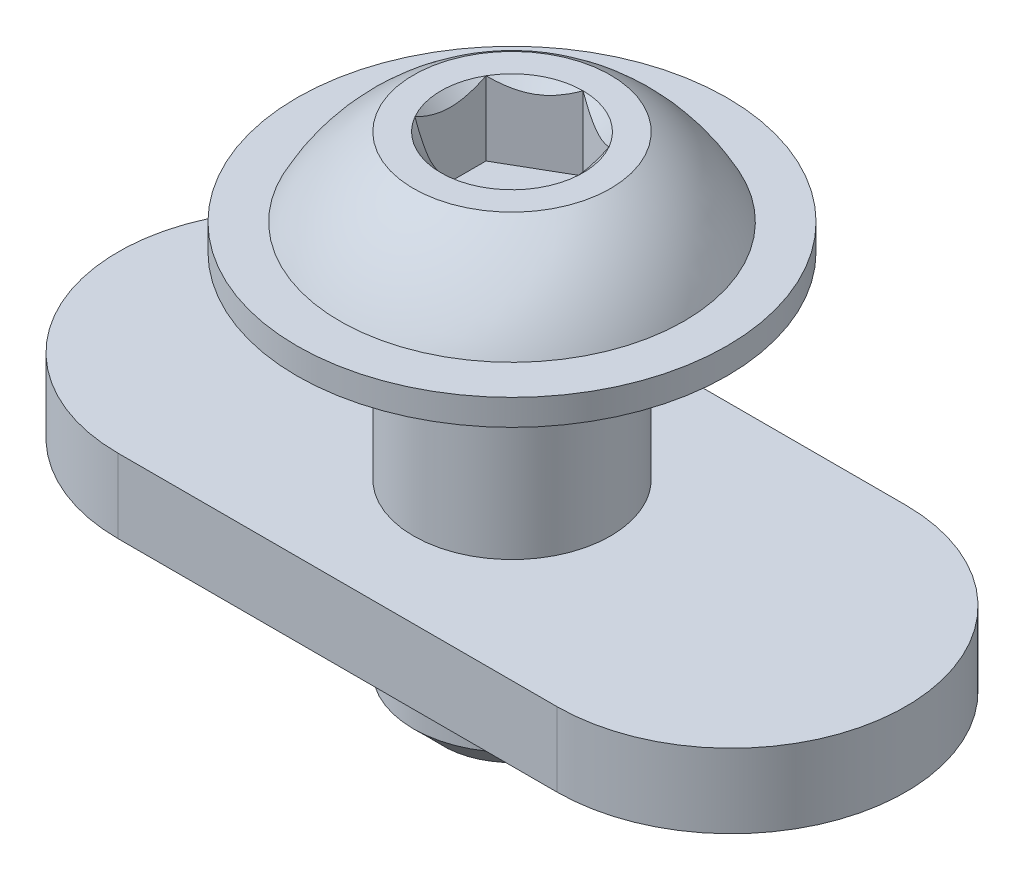
SolidWorks part; units mm, degrees
ref_plane "Front Plane" through (0, 0, 0) normal (0, 0, 1) x (1, 0, 0)
ref_plane "Top Plane" through (0, 0, 0) normal (0, 1, 0) x (1, 0, 0)
ref_plane "Right Plane" through (0, 0, 0) normal (1, 0, 0) x (0, 0, -1)
sketch "Sketch1" plane through (0, 0, 0) normal (0, 1, 0) x (1, 0, 0)
  circle A0 centre (0, 0) radius 3.175
  point P3 (-3.175, 0)
  point P4 (3.175, 0)
  dimension "D1" = 6.35
extrude "Boss-Extrude1" add sketch "Sketch1" against normal blind 12.7
sketch "Sketch2" plane through (0, -12.7, 0) normal (0, -1, 0) x (1, 0, 0)
  circle A1 centre (0, 0) radius 3.175
  circle A2 centre (0, 0) radius 3.175
  point P0 (0, -3.175)
  dimension "D1" = 0
curve "Helix/Spiral1" [suppressed] pitch 1.27 height 13.97 turns 11
sketch "Sketch3" plane through (0, 0, 0) normal (1, 0, 0) x (0, 0, -1)
  line L0 (3.3125, -12.6206) -> (2.2126, -13.2556) construction
  line L1 (2.2126, -13.2556) -> (3.3125, -13.8906) construction
  line L2 (3.3125, -13.8906) -> (3.3125, -12.6206) construction
  line L3 (2.3501, -13.1762) -> (2.3501, -13.335) construction
  line L4 (3.175, -12.7) -> (3.175, -13.8112) construction
  line L5 (2.2126, -13.2556) -> (2.3501, -13.2556) construction
  line L6 (3.175, -13.2556) -> (3.3125, -13.2556) construction
  line L8 (2.2126, -13.2556) -> (-3.175, -13.2556) construction
  line L9 (2.3501, -13.1762) -> (3.2437, -12.6603)
  line L10 (2.3501, -13.1762) -> (2.3501, -13.335)
  line L11 (2.3501, -13.335) -> (3.2437, -13.8509)
  line L12 (3.2437, -13.8509) -> (3.2437, -12.6603)
  line L14 (-3.175, -13.2556) -> (-3.175, -11.9856) construction
  line L15 (-3.175, -11.9856) -> (-3.175, -10.7156) construction
  line L16 (-3.175, -10.7156) -> (-3.175, -9.4456) construction
  line L17 (-3.175, -9.4456) -> (-3.175, -8.1756) construction
  line L18 (-3.175, 0) -> (-3.175, -12.7) construction
  point P15 (3.2437, -13.2556)
  dimension "D1" = 1.27
  dimension "D2" = 0.1588
sweep "Cut-Sweep1" [suppressed] cut profiles "Sketch3" path "Helix/Spiral1"
sketch "Sketch4" plane through (0, -12.7, 0) normal (0, -1, 0) x (1, 0, 0)
  circle A0 centre (0, 0) radius 2.2126
extrude "Cut-Extrude1" cut sketch "Sketch4" against normal blind 1.27 draft 45 flip side to cut
sketch "Sketch5" plane through (0, 0, 0) normal (0, 0, 1) x (1, 0, 0)
  line L0 (0, 0) -> (0, 3.3528)
  line L1 (-6.9342, 0) -> (0, 0)
  line L2 (0, 3.3528) -> (-3.175, 3.3528)
  line L3 (-5.5499, 0.8382) -> (-6.9342, 0.8382)
  line L4 (-6.9342, 0.8382) -> (-6.9342, 0)
  line L5 (0, 0) -> (0, -12.7) construction
  arc A0 (-3.175, 3.3528) -> (-5.5499, 0.8382) centre (0, -2.0246) ccw
  dimension "D1" = 3.3528
  dimension "D2" = 0.8382
  dimension "D3" = 13.8684
  dimension "D4" = 11.0998
revolve "Revolve1" add sketch "Sketch5" angle 360 mid plane about L0
sketch "Sketch6" plane through (0, 3.3528, 0) normal (0, 1, 0) x (1, 0, 0)
  line L1 (0, 2.2914) -> (-1.9844, 1.1457)
  line L2 (-1.9844, 1.1457) -> (-1.9844, -1.1457)
  line L3 (-1.9844, -1.1457) -> (0, -2.2914)
  line L4 (0, -2.2914) -> (1.9844, -1.1457)
  line L5 (1.9844, -1.1457) -> (1.9844, 1.1457)
  line L6 (1.9844, 1.1457) -> (0, 2.2914)
  circle A0 centre (0, 0) radius 1.9844 construction
  dimension "D1" = 3.9688
extrude "Cut-Extrude2" cut sketch "Sketch6" against normal blind 2.3813
sketch "Sketch7" plane through (0, 3.3528, 0) normal (0, 1, 0) x (1, 0, 0)
  circle A0 centre (0, 0) radius 2.2914
extrude "Cut-Extrude3" cut sketch "Sketch7" against normal blind 2.3813 draft 45
sketch "Sketch8" plane through (0, 0, 0) normal (0, 1, 0) x (1, 0, 0)
  line L0 (-7.0739, 0) -> (7.0739, 0) construction
  line L1 (-7.0739, 5.6261) -> (7.0739, 5.6261)
  line L2 (-7.0739, -5.6261) -> (7.0739, -5.6261)
  line L4 (-12.7, 5.6261) -> (12.7, 5.6261) construction
  line L5 (-12.7, 5.6261) -> (-12.7, -5.6261) construction
  line L6 (-12.7, -5.6261) -> (12.7, -5.6261) construction
  line L7 (12.7, 5.6261) -> (12.7, -5.6261) construction
  arc A0 (-7.0739, 5.6261) -> (-7.0739, -5.6261) centre (-7.0739, 0) ccw
  arc A1 (7.0739, -5.6261) -> (7.0739, 5.6261) centre (7.0739, 0) ccw
  circle A3 centre (0, 0) radius 3.175
  circle A4 centre (0, 0) radius 3.175
  point P2 (0, 0)
  dimension "D2" = 25.4
  dimension "D3" = 11.2522
  dimension "D1" = 0
extrude "Boss-Extrude2" add sketch "Sketch8" against normal blind 2.3876 from offset 6.35 separate body offset against normal yes
sketch "Sketch9" plane through (0, -8.7376, 0) normal (0, -1, 0) x (1, 0, 0)
  circle A1 centre (0, 0) radius 3.175 construction
  circle A2 centre (0, 0) radius 3.175
  circle A3 centre (0, 0) radius 3.5687
  dimension "D1" = 7.1374
extrude "Boss-Extrude3" add sketch "Sketch9" along normal blind 0.762
sketch "SketchZ" plane through (0, 0, 0) normal (0, 0, 1) x (1, 0, 0)
  line L0 (3.175, -12.9381) -> (3.175, -11.6681) construction
  line L2 (0, -13.2556) -> (0, -11.9856) construction
  line L4 (3.175, -12.9381) -> (0, -12.9381) construction
  line L5 (0, -9.4456) -> (0, -8.1756) construction
  line L6 (0, -12.6206) -> (0, -13.2556) construction
equation "\"D3@Helix/Spiral1\" = \"D4@Helix/Spiral1\" + \"D1@Boss-Extrude1\""
equation "\"D1@Sketch3\" = \"D4@Helix/Spiral1\""
equation "\"D2@Sketch3\" = \"D1@Sketch3\" / 8"
equation "\"D1@Cut-Extrude1\" = \"D4@Helix/Spiral1\""
equation "\"D1@Cut-Extrude2\" = \"D1@Sketch6\" * 3/5"
equation "\"D1@Cut-Extrude3\" = \"D1@Cut-Extrude2\""
equation "\"D2@Sketch5\" = \"D1@Sketch5\" * 1/4"
